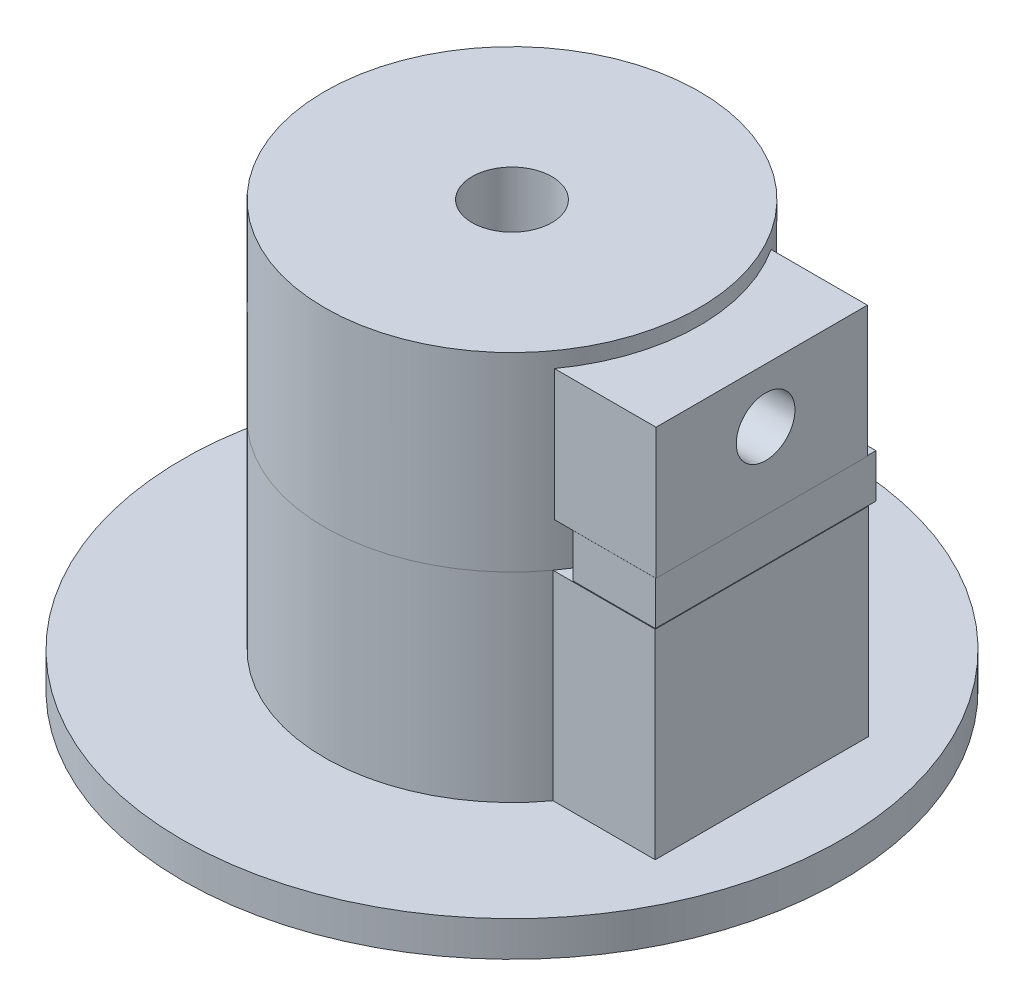
SolidWorks part; units mm, degrees
ref_plane "Front Plane" through (0, 0, 0) normal (0, 0, 1) x (1, 0, 0)
ref_plane "Top Plane" through (0, 0, 0) normal (0, 1, 0) x (1, 0, 0)
ref_plane "Right Plane" through (0, 0, 0) normal (1, 0, 0) x (0, 0, -1)
sketch "Sketch1" plane through (0, 0, 0) normal (0, 1, 0) x (1, 0, 0)
  circle A0 centre (0, 0) radius 15.958
extrude "ShaftHolderNearMotor" add sketch "Sketch1" along normal blind 17.19
sketch "Sketch2" plane through (0, 17.19, 0) normal (0, 1, 0) x (1, 0, 0)
  circle A0 centre (0, 0) radius 3.4
extrude "ShaftHole" cut sketch "Sketch2" against normal blind 16.85 contours A0
ref_plane "Plane1" through (0, 12.15, 0) normal (0, 1, 0) x (1, 0, 0)
ref_axis "Axis1" through (0, -74.793, 0) along (0, 1, 0)
ref_point "Point2"
sketch "Sketch5" plane through (0, 12.15, 0) normal (0, 1, 0) x (1, 0, 0)
  line L0 (0, 0) -> (2.6, 0) construction
  line L2 (2.6, -3.5716) -> (4.1507, -3.5716)
  line L3 (2.6, -3.5716) -> (2.6, 3.6126)
  line L4 (2.6, 3.6126) -> (4.1507, 3.6126)
  line L5 (4.1507, -3.5716) -> (4.1507, 3.6126)
extrude "Boss-Extrude2" add sketch "Sketch5" against normal blind 13.55
sketch "Sketch7" plane through (2.6, 0, 0) normal (-1, 0, 0) x (0, 0, 1)
  line L1 (-8.6717, 14.8677) -> (9.3323, 14.8677)
  line L2 (-8.6717, 14.8677) -> (-8.6717, 3.7227)
  line L3 (-8.6717, 3.7227) -> (9.3323, 3.7227)
  line L4 (9.3323, 14.8677) -> (9.3323, 3.7227)
extrude "Boss-Extrude3" add sketch "Sketch7" against normal blind 19
sketch "Sketch6" plane through (2.6, 0, 0) normal (-1, 0, 0) x (0, 0, 1)
  line L1 (-2.1909, 0.34) -> (-2.1909, 14.8677) construction
  line L2 (2.1909, 14.8677) -> (2.1909, 0.34) construction
  line L3 (-2.1909, 15.4522) -> (2.1909, 15.4522) construction
  circle A0 centre (0, 10.2369) radius 2.5
extrude "BoltHole" cut sketch "Sketch6" against normal up to surface (19 mm away) and the other way blind 1 up to face at (21.6, 9.2952, 0.3303)
ref_axis "Axis2" through (-1.8994, 10.2369, 0) along (-1, 0, 0)
ref_axis "Axis4" through (21.6, 10.2369, 0) along (-1, 0, 0)
ref_plane "Plane3" through (0, 0, 0) normal (0, 0, 1) x (1, 0, 0)
sketch "Sketch10" plane through (0, 0, 0) normal (0, -1, 0) x (1, 0, 0)
  circle A0 centre (0, 0) radius 50
extrude "Boss-Extrude4" add sketch "Sketch10" along normal blind 20
sketch "Sketch11" plane through (0, 0, 0) normal (0, 1, 0) x (1, 0, 0)
  line L1 (31.7817, 38.8528) -> (14.4942, 48.0577) construction
  line L2 (14.4942, 48.0577) -> (-5, 49.9462) construction
  line L3 (-5, 49.9462) -> (-23.733, 44.2308) construction
  line L4 (-23.733, 44.2308) -> (-38.8528, 31.7817) construction
  line L5 (-38.8528, 31.7817) -> (-48.0577, 14.4942) construction
  line L6 (-48.0577, 14.4942) -> (-49.9462, -5) construction
  line L7 (-49.9462, -5) -> (-44.2308, -23.733) construction
  line L8 (-44.2308, -23.733) -> (-31.7817, -38.8528) construction
  line L9 (-31.7817, -38.8528) -> (-14.4942, -48.0577) construction
  line L10 (-14.4942, -48.0577) -> (5, -49.9462) construction
  line L11 (5, -49.9462) -> (23.733, -44.2308) construction
  line L12 (23.733, -44.2308) -> (38.8528, -31.7817) construction
  line L13 (38.8528, -31.7817) -> (48.0577, -14.4942) construction
  line L14 (48.0577, -14.4942) -> (49.9462, 5) construction
  line L15 (49.9462, 5) -> (44.2308, 23.733) construction
  line L16 (44.2308, 23.733) -> (31.7817, 38.8528) construction
  circle A0 centre (0, 0) radius 49.2313 construction
  circle A1 centre (5, -49.9462) radius 5
  circle A2 centre (-14.4942, -48.0577) radius 5
  circle A3 centre (-31.7817, -38.8528) radius 5
  circle A4 centre (-44.2308, -23.733) radius 5
  circle A5 centre (-49.9462, -5) radius 5
  circle A6 centre (-48.0577, 14.4942) radius 5
  circle A7 centre (-38.8528, 31.7817) radius 5
  circle A8 centre (-23.733, 44.2308) radius 5
  circle A9 centre (-5, 49.9462) radius 5
  circle A10 centre (14.4942, 48.0577) radius 5
  circle A11 centre (31.7817, 38.8528) radius 5
  circle A12 centre (44.2308, 23.733) radius 5
  circle A13 centre (49.9462, 5) radius 5
  circle A14 centre (48.0577, -14.4942) radius 5
  circle A15 centre (38.8528, -31.7817) radius 5
  circle A16 centre (23.733, -44.2308) radius 5
sketch "Sketch12" plane through (0, 0, 0) normal (0, 1, 0) x (1, 0, 0)
  circle A0 centre (0, 0) radius 43
  circle A1 centre (0, 0) radius 15.9579
extrude "CutToRemveExcessMaterial" cut sketch "Sketch12" against normal offset from surface (17 mm away) 3 up to face at (0, -20, -50)
sketch "Sketch13" plane through (0, 0, 0) normal (0, 1, 0) x (1, 0, 0)
  circle A0 centre (0, 0) radius 42.6967
  circle A1 centre (0, 0) radius 50
extrude "Boss-Extrude5" add sketch "Sketch13" along normal blind 17
sketch "Sketch9" plane through (0, 0, 0) normal (0, 0, 1) x (1, 0, 0)
  line L0 (11.8765, 10.2369) -> (11.8765, 5.9284) construction
  line L1 (4.9434, 5.9284) -> (11.8765, 5.9284) construction
  line L2 (4.9434, 5.9284) -> (4.9434, 10.2369) construction
  line L3 (4.9434, 10.2369) -> (4.9434, 14.4709) construction
  line L4 (4.9434, 14.4709) -> (11.8765, 14.4709) construction
  line L5 (11.8765, 14.4709) -> (11.8765, 10.2369) construction
  line L6 (21.6, 10.2369) -> (2.1647, 10.2369) construction
  line L7 (4.9434, 14.4709) -> (11.8765, 5.9284) construction
  line L8 (4.9434, 14.4709) -> (2.2275, 17.8172) construction
  line L9 (11.8765, 5.9284) -> (13.8816, 3.4579) construction
  line L11 (4.6498, 14.8327) -> (12.177, 14.8327) construction
  line L12 (4.6498, 14.8327) -> (4.6498, 5.5583) construction
  line L13 (4.6498, 5.5583) -> (12.177, 5.5583) construction
  line L14 (12.177, 14.8327) -> (12.177, 5.5583) construction
  line L15 (4.8683, 14.5635) -> (11.954, 14.5635)
  line L16 (4.8683, 14.5635) -> (4.8683, 5.8329)
  line L17 (4.8683, 5.8329) -> (11.954, 5.8329)
  line L18 (11.954, 14.5635) -> (11.954, 5.8329)
  circle A0 centre (4.9434, 14.4709) radius 0.466 construction
  circle A1 centre (11.8765, 5.9284) radius 0.4768 construction
  circle A2 centre (4.9434, 14.4709) radius 0.423 construction
  circle A3 centre (11.8765, 5.9284) radius 0.423 construction
  circle A4 centre (4.9434, 14.4709) radius 0.123 construction
  circle A5 centre (11.8765, 5.9284) radius 0.123 construction
  point P23 (12.0155, 5.7862)
  point P24 (11.954, 5.8329)
extrude "NutOpening" cut sketch "Sketch9" against normal through all
sketch "Sketch14" plane through (11.954, 0, 0) normal (-1, 0, 0) x (0, 0, 1)
  line L1 (-4.7319, 10.2369) -> (-2.366, 6.139)
  line L2 (-2.366, 6.139) -> (2.366, 6.139)
  line L3 (2.366, 6.139) -> (4.7319, 10.2369)
  line L4 (4.7319, 10.2369) -> (2.366, 14.3349)
  line L5 (2.366, 14.3349) -> (-2.366, 14.3349)
  line L6 (-2.366, 14.3349) -> (-4.7319, 10.2369)
  circle A0 centre (0, 10.2369) radius 4.098 construction
extrude "HexCut" cut sketch "Sketch14" along normal up to surface (7.0857 mm away) up to face at (4.8683, 10.2111, -5.4824)
sketch "Sketch16" plane through (21.6, 0, 0) normal (1, 0, 0) x (0, 0, -1)
  circle A0 centre (0, 10.2369) radius 6
extrude "Cut-Extrude7" cut sketch "Sketch16" along normal blind 40
ref_plane "Plane4" through (-0.571, 0, -49.9967) normal (-0.0114, 0, -0.9999) x (-0.9999, 0, 0.0114)
ref_plane "Plane5" through (-27.4359, 0, -41.8004) normal (-0.5487, 0, -0.836) x (-0.836, 0, 0.5487)
sketch "Sketch17" plane through (-0.571, 0, -49.9967) normal (-0.0114, 0, -0.9999) x (-0.9999, 0, 0.0114)
  line L1 (-6.9779, 26.3682) -> (19.0025, 26.3682)
sketch "Sketch18" plane through (-27.4359, 0, -41.8004) normal (-0.5487, 0, -0.836) x (-0.836, 0, 0.5487)
  line L1 (2.3429, -8.8145) -> (-7.3736, -8.8145)
  line L2 (2.3429, -8.8145) -> (2.3429, -36.514)
  line L3 (2.3429, -36.514) -> (-7.3736, -36.514)
  line L4 (-7.3736, -8.8145) -> (-7.3736, -36.514)
ref_plane "Plane6" through (18.6054, 0, -46.4095) normal (0.3721, 0, -0.9282) x (-0.9282, 0, -0.3721)
ref_plane "Plane7" through (34.9493, 0, -35.7568) normal (0.699, 0, -0.7151) x (-0.7151, 0, -0.699)
ref_plane "Plane8" through (45.9725, 0, -19.6605) normal (0.9194, 0, -0.3932) x (-0.3932, 0, -0.9194)
ref_plane "Plane9" through (49.1178, 0, -9.3511) normal (0.9824, 0, -0.187) x (-0.187, 0, -0.9824)
ref_plane "Plane10" through (46.4095, 0, 18.6054) normal (0.9282, 0, 0.3721) x (0.3721, 0, -0.9282)
ref_plane "Plane11" through (35.7568, 0, 34.9493) normal (0.7151, 0, 0.699) x (0.699, 0, -0.7151)
ref_plane "Plane12" through (9.3511, 0, 49.1178) normal (0.187, 0, 0.9824) x (0.9824, 0, -0.187)
ref_plane "Plane13" through (-28.1193, 0, 41.3438) normal (-0.5624, 0, 0.8269) x (0.8269, 0, 0.5624)
ref_plane "Plane14" through (-49.1178, 0, 9.3511) normal (-0.9824, 0, 0.187) x (0.187, 0, 0.9824)
ref_plane "Plane15" through (-41.3438, 0, -28.1193) normal (-0.8269, 0, -0.5624) x (-0.5624, 0, 0.8269)
sketch "Sketch19" plane through (9.3511, 0, 49.1178) normal (0.187, 0, 0.9824) x (0.9824, 0, -0.187)
  circle A0 centre (-6.5538, -15.0444) radius 12
extrude "Cut-Extrude8" cut sketch "Sketch19" against normal blind 5
sketch "Sketch20" plane through (35.7568, 0, 34.9493) normal (0.7151, 0, 0.699) x (0.699, 0, -0.7151)
  circle A0 centre (3.5584, 19.4292) radius 12
extrude "Cut-Extrude9" cut sketch "Sketch20" against normal blind 5
sketch "Sketch21" plane through (49.1178, 0, -9.3511) normal (0.9824, 0, -0.187) x (-0.187, 0, -0.9824)
  circle A0 centre (-4.7912, -19.2219) radius 10
sketch "Sketch22" plane through (34.9493, 0, -35.7568) normal (0.699, 0, -0.7151) x (-0.7151, 0, -0.699)
  circle A0 centre (5.4277, 18.4908) radius 12.5535
extrude "Cut-Extrude10" cut sketch "Sketch22" against normal blind 5
extrude "Cut-Extrude11" cut sketch "Sketch21" against normal blind 5 contours A0
sketch "Sketch23" plane through (-0.571, 0, -49.9967) normal (-0.0114, 0, -0.9999) x (-0.9999, 0, 0.0114)
  circle A0 centre (4.5252, -20.0178) radius 11.9653
extrude "Cut-Extrude12" cut sketch "Sketch23" against normal blind 5
sketch "Sketch25" plane through (-41.3438, 0, -28.1193) normal (-0.8269, 0, -0.5624) x (-0.5624, 0, 0.8269)
  circle A0 centre (-2.6498, 18.6432) radius 9.6297
extrude "Cut-Extrude13" cut sketch "Sketch25" against normal blind 5
sketch "Sketch26" plane through (-49.1178, 0, 9.3511) normal (-0.9824, 0, 0.187) x (0.187, 0, 0.9824)
  circle A0 centre (-4.4977, -19.1264) radius 15.0124
extrude "Cut-Extrude14" cut sketch "Sketch26" against normal blind 5
sketch "Sketch27" plane through (-28.1193, 0, 41.3438) normal (-0.5624, 0, 0.8269) x (0.8269, 0, 0.5624)
  circle A0 centre (-2.2875, 17.6222) radius 11.8547
extrude "Cut-Extrude15" cut sketch "Sketch27" against normal blind 5
sketch "Sketch28" plane through (0, 0, 0) normal (0, -1, 0) x (1, 0, 0)
  line L1 (12.7613, 9.4042) -> (21.6, 9.4042)
  line L2 (12.7613, 9.4042) -> (12.7613, -8.7683)
  line L3 (12.7613, -8.7683) -> (21.6, -8.7683)
  line L4 (21.6, 9.4042) -> (21.6, -8.7683)
extrude "Boss-Extrude6" add sketch "Sketch28" along normal up to surface (17 mm away) up to face at (0, -17, -43)
sketch "Sketch29" plane through (0, 3.7227, 0) normal (0, -1, 0) x (1, 0, 0)
  line L1 (21.5487, 9.3378) -> (14.5231, 9.3378)
  line L2 (21.5487, 9.3378) -> (21.5487, -9.4483)
  line L3 (21.5487, -9.4483) -> (14.5231, -9.4483)
  line L4 (14.5231, 9.3378) -> (14.5231, -9.4483)
extrude "Boss-Extrude7" add sketch "Sketch29" along normal up to surface (3.7227 mm away) up to face at (18.0666, 0, 0.3352)
sketch "Sketch30" plane through (0, 17.19, 0) normal (0, 1, 0) x (1, 0, 0)
  circle A0 centre (0, 0) radius 3.4
  circle A1 centre (0, 0) radius 8.7876
sketch "Sketch31" plane through (0, 17.19, 0) normal (0, 1, 0) x (1, 0, 0)
  circle A0 centre (0, 0) radius 26.3365
extrude "Cut-Extrude16" cut sketch "Sketch31" against normal blind 1
sketch "Sketch32" plane through (0, 14.8677, 0) normal (0, 1, 0) x (1, 0, 0)
  circle A0 centre (0, 0) radius 3.3803
extrude "Cut-Extrude17" cut sketch "Sketch32" against normal blind 2
ref_point "Point4"
sketch "Sketch33" plane through (0, -20, 0) normal (0, -1, 0) x (1, 0, 0)
  circle A0 centre (0, 0) radius 28.0686
  circle A1 centre (0, 0) radius 63.3241
extrude "RemoveOutsideOfWheel(WouldLikeToDisableThis)" cut sketch "Sketch33" against normal through all
sketch "Sketch37" plane through (4.8683, 0, 0) normal (1, 0, 0) x (0, 0, -1)
  line L0 (15.1973, 5.8329) -> (14.3236, 3.3685)
  line L1 (14.3236, 3.3685) -> (5.9217, 5.8329)
  line L2 (15.1973, 5.8329) -> (0, 5.8329) construction
  line L3 (5.9217, 5.8329) -> (15.1973, 5.8329)
extrude "CutOutWedgeToMakeBotInsertionEasier" cut sketch "Sketch37" along normal up to surface (7.0857 mm away) up to face at (11.954, 10.2197, -1.2977)
sketch "Sketch38" plane through (11.954, 0, 0) normal (-1, 0, 0) x (0, 0, 1)
  line L0 (2.366, 6.139) -> (3.2372, 6.139)
  line L1 (3.2372, 6.139) -> (5.7391, 10.2262)
  line L2 (5.7391, 10.2262) -> (3.237, 14.561)
  line L3 (3.237, 14.561) -> (2.366, 14.3349)
  line L4 (2.366, 6.139) -> (4.7319, 10.2369)
  line L5 (4.7319, 10.2369) -> (2.366, 14.3349)
extrude "BoltHolderDepthIncrease" cut sketch "Sketch38" along normal up to surface (7.0857 mm away) up to face at (4.8683, 9.1981, -3.7433)
